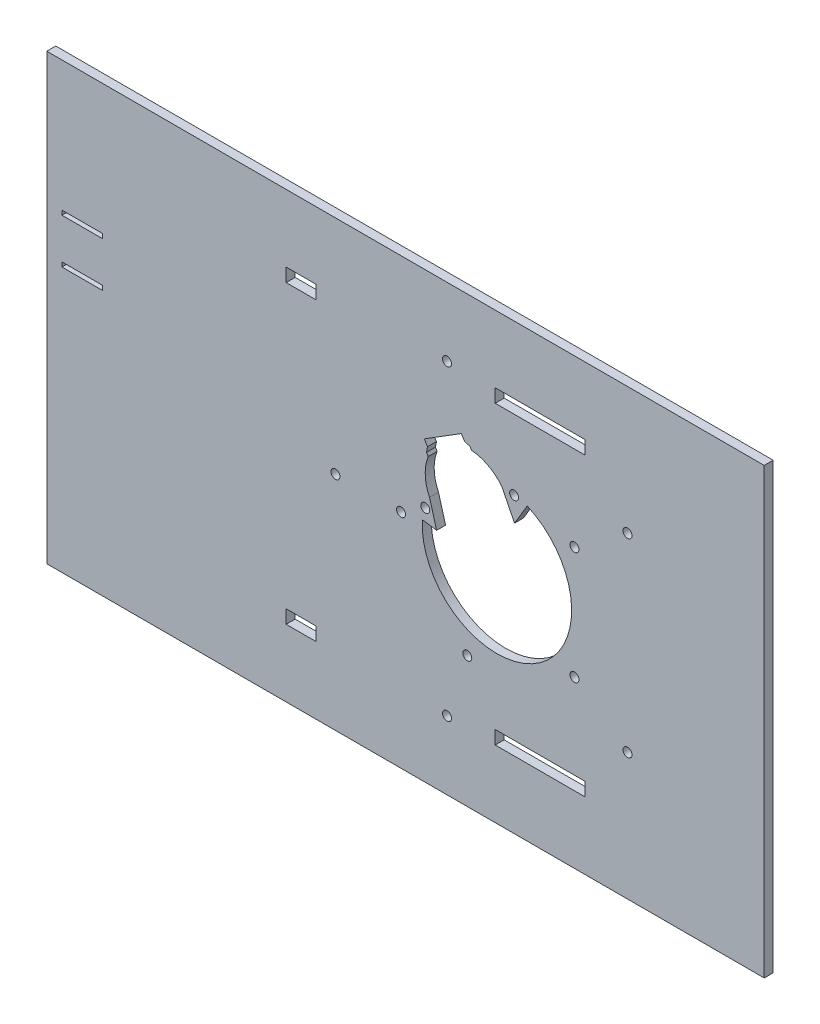
SolidWorks part; units mm, degrees
ref_plane "Front Plane" through (0, 0, 0) normal (0, 0, 1) x (1, 0, 0)
ref_plane "Top Plane" through (0, 0, 0) normal (0, 1, 0) x (1, 0, 0)
ref_plane "Right Plane" through (0, 0, 0) normal (1, 0, 0) x (0, 0, -1)
sketch "Sketch1" plane through (0, 0, 0) normal (0, 0, 1) x (1, 0, 0)
  line L0 (-120.0004, 74.2497) -> (-120.0004, -74.2497)
  line L1 (-120.0004, -74.2497) -> (120.0004, -74.2497)
  line L2 (120.0004, -74.2497) -> (120.0004, 74.2497)
  line L3 (120.0004, 74.2497) -> (-120.0004, 74.2497)
  line L4 (-114.931, 29.2525) -> (-101.4295, 29.2525)
  line L5 (-114.931, 30.7526) -> (-101.4295, 30.7526)
  line L6 (-114.931, 15.751) -> (-101.4295, 15.751)
  line L7 (-114.931, 14.2498) -> (-101.4295, 14.2498)
  line L8 (-39.9319, 51.7498) -> (-39.9319, 47.2493)
  line L9 (-39.9319, 47.2493) -> (-30.0013, 47.2493)
  line L10 (-30.0013, 47.2493) -> (-30.0013, 51.7498)
  line L11 (-30.0013, 51.7498) -> (-39.9319, 51.7498)
  line L12 (29.9987, 51.7498) -> (29.9987, 47.2493)
  line L13 (29.9987, 47.2493) -> (59.9984, 47.2493)
  line L14 (59.9984, 47.2493) -> (59.9984, 51.7498)
  line L15 (59.9984, 51.7498) -> (29.9987, 51.7498)
  line L16 (-39.9319, -47.2483) -> (-30.0013, -47.2483)
  line L17 (-30.0013, -47.2483) -> (-30.0013, -51.7488)
  line L18 (-30.0013, -51.7488) -> (-39.9319, -51.7488)
  line L19 (-39.9319, -51.7488) -> (-39.9319, -47.2483)
  line L20 (30.0002, -47.2483) -> (60.0005, -47.2483)
  line L21 (60.0005, -47.2483) -> (60.0005, -51.7488)
  line L22 (60.0005, -51.7488) -> (30.0002, -51.7488)
  line L23 (30.0002, -51.7488) -> (30.0002, -47.2483)
  line L24 (-101.4295, 29.2525) -> (-101.4295, 30.7526)
  line L25 (-114.931, 30.7526) -> (-114.931, 29.2525)
  line L26 (-114.931, 15.751) -> (-114.931, 14.2498)
  line L27 (-101.4295, 15.751) -> (-101.4295, 14.2498)
  circle A0 centre (30.5702, 0.0013) radius 25
  dimension "D2" = 50
  dimension "D1" = 240.0009
extrude "Boss-Extrude2" add sketch "Sketch1" along normal blind 3
sketch "Sketch5" plane through (0, 0, 3) normal (0, 0, 1) x (1, 0, 0)
  circle A0 centre (30.5702, 0.0013) radius 54
  circle A1 centre (-23.4298, 0.0013) radius 1.5
  circle A2 centre (13.8833, 51.3583) radius 1.5
  circle A3 centre (74.2571, 31.7417) radius 1.5
  circle A4 centre (74.2571, -31.7391) radius 1.5
  circle A5 centre (13.8833, -51.3558) radius 1.5
  point P15 (30.5702, 0.0013)
  dimension "D1" = 5
extrude "Cut-Extrude4" cut sketch "Sketch5" against normal blind 10 contours A1 | A2 | A3 | A4 | A5
sketch "Sketch6" plane through (0, 0, 3) normal (0, 0, 1) x (1, 0, 0)
  circle A0 centre (30.5702, 0.0013) radius 32.0702
  circle A1 centre (-1.5, 0.0013) radius 1.5
  circle A2 centre (20.66, -30.4993) radius 1.5
  circle A3 centre (56.5156, -18.8491) radius 1.5
  circle A4 centre (56.5156, 18.8517) radius 1.5
  circle A5 centre (20.66, 30.5019) radius 1.5
  point P17 (30.5702, 0.0013)
  dimension "D1" = 5
extrude "Cut-Extrude5" cut sketch "Sketch6" against normal blind 10 contours A1 | A2 | A3 | A4
sketch "Sketch9" plane through (0, 0, 3) normal (0, 0, 1) x (1, 0, 0)
  line L0 (30.5702, 0.0013) -> (29.7765, 1.2741) construction
  line L1 (25.279, 8.4867) -> (21.046, 15.2751) construction
  line L2 (17.3421, 21.2149) -> (43.7983, -21.2123) construction
  line L3 (25.279, 8.4867) -> (21.046, 15.2751) construction
  line L4 (21.046, 15.2751) -> (6.1965, 6.0154) construction
  line L5 (6.1965, 6.0154) -> (35.8955, 24.5348) construction
  line L6 (42.529, 23.914) -> (3.4467, 0.228)
  circle A0 centre (30.5702, 0.0013) radius 10
  circle A1 centre (30.5702, 0.0013) radius 25 construction
  circle A2 centre (25.279, 8.4867) radius 8.5
  arc A3 (42.529, 23.914) -> (3.4467, 0.228) centre (21.046, 15.2751) ccw
  circle A4 centre (21.046, 15.2751) radius 14.5
  dimension "D1" = 15
  dimension "D2" = 17
  dimension "D3" = 8
  dimension "D4" = 17.5
  dimension "D5" = 35
extrude "Cut-Extrude6" cut sketch "Sketch9" against normal blind 10 contours A4
sketch "Sketch13" plane through (0, 0, 3) normal (0, 0, 1) x (1, 0, 0)
  line L0 (32.2445, 24.2147) -> (36.4646, 15.7366)
  line L1 (36.4646, 15.7366) -> (45.0058, 30.0467)
  line L2 (-2.6896, 2.5867) -> (10.3964, 0.624)
  line L3 (10.3964, 0.624) -> (8.0115, 9.1038)
  arc A0 (45.0058, 30.0467) -> (-2.6896, 2.5867) centre (29.0903, 2.5392) ccw
  arc A1 (32.2445, 24.2147) -> (8.085, 8.9269) centre (20.9521, 15.3265) ccw
  circle A2 centre (36.3114, 23.7799) radius 1.5
  circle A3 centre (6.6123, 5.2605) radius 1.5
  arc M1 (7.5956, 9.8586) -> (31.8287, 24.9696) centre (21.046, 15.2751) cw
  arc M2 (31.8287, 24.9696) -> (7.5956, 9.8586) centre (30.5702, 0.0013) cw
extrude "Boss-Extrude4" add sketch "Sketch13" against normal blind 3 contours A3 L2 L3 A1 L0 L1 A2 M2 M1 region at (8.7737, 4.7082, 3)
sketch "Sketch14" plane through (0, 0, 3) normal (0, 0, 1) x (1, 0, 0)
  circle A0 centre (36.3114, 23.7799) radius 1.5
  circle A1 centre (6.6123, 5.2605) radius 1.5
extrude "Cut-Extrude7" cut sketch "Sketch14" against normal blind 3
sketch "Sketch15" plane through (0, 0, 0) normal (0, 0, -1) x (-1, 0, 0)
  line L1 (-21.5282, 30.5725) -> (-19.7478, 31.0653)
  line L2 (-19.7478, 31.0653) -> (-21.5282, 30.5725) construction
  line L3 (-19.7478, 31.0653) -> (-18.6611, 32.8081)
  line L4 (-18.6611, 32.8081) -> (-6.2723, 25.0828)
  line L5 (-6.2723, 25.0828) -> (-7.3591, 23.34)
  line L6 (-7.3591, 23.34) -> (-7.0181, 21.5244)
  line L7 (-7.0181, 21.5244) -> (-7.6795, 20.4637)
  line L8 (-8.341, 19.4031) -> (-7.0181, 21.5244) construction
  line L9 (-7.6795, 20.4637) -> (-22.1897, 29.5118)
  line L10 (-21.5282, 30.5725) -> (-22.8511, 28.4511) construction
  line L11 (-22.1897, 29.5118) -> (-21.5282, 30.5725)
extrude "Cut-Extrude8" cut sketch "Sketch15" against normal blind 10
